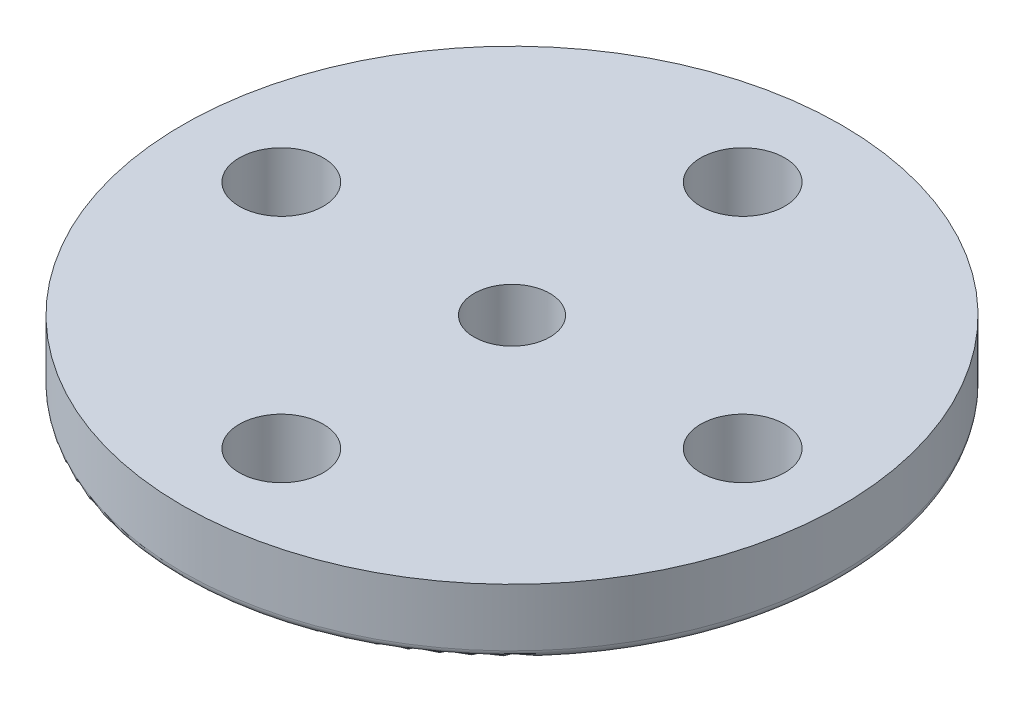
SolidWorks part; units mm, degrees
material "ABS"
ref_plane "Front Plane" through (0, 0, 0) normal (0, 0, 1) x (1, 0, 0)
ref_plane "Top Plane" through (0, 0, 0) normal (0, 1, 0) x (1, 0, 0)
ref_plane "Right Plane" through (0, 0, 0) normal (1, 0, 0) x (0, 0, -1)
sketch "Sketch1" plane through (0, 0, 0) normal (0, 1, 0) x (1, 0, 0)
  circle A0 centre (0, 0) radius 10
  dimension "D1" = 20
extrude "Boss-Extrude1" add sketch "Sketch1" along normal blind 2
sketch "Sketch2" plane through (0, 0, 0) normal (0, 1, 0) x (1, 0, 0)
  circle A0 centre (0, 0) radius 4.5
  dimension "D1" = 9
extrude "Boss-Extrude2" add sketch "Sketch2" against normal blind 3.5
sketch "Sketch3" plane through (0, 0, 0) normal (0, 1, 0) x (1, 0, 0)
  line L0 (0, 16.6668) -> (0, -17.2828) construction
  line L1 (-21.9372, 0) -> (30.2192, 0) construction
  line L2 (-7, 16.6668) -> (-7, -16.6668) construction
  line L3 (-15.9139, 7) -> (17.4197, 7) construction
  circle A0 centre (0, 7) radius 1.275
  circle A1 centre (-7, 0) radius 1.275
  circle A2 centre (0, -7) radius 1.275
  circle A3 centre (7, 0) radius 1.275
  dimension "D3" = 2.55
  dimension "D4" = 2.55
  dimension "D1" = 7
  dimension "D2" = 7
extrude "Cut-Extrude1" cut sketch "Sketch3" along normal through all
cosmetic thread "Cosmetic Thread1" parameters "D2"=2.87
cosmetic thread "Cosmetic Thread2" parameters "D2"=2.87
cosmetic thread "Cosmetic Thread3" parameters "D2"=2.87
cosmetic thread "Cosmetic Thread4" parameters "D2"=2.87
fillet "Fillet1" radius 0.25 1 edges at (0, 0, 10)
sketch "Sketch6" plane through (0, 2, 0) normal (0, 1, 0) x (1, 0, 0)
  circle A0 centre (0, 0) radius 1.15
  dimension "D1" = 2.3
extrude "Cut-Extrude2" cut sketch "Sketch6" against normal through all
sketch "Sketch7" plane through (0, -3.5, 0) normal (0, -1, 0) x (1, 0, 0)
  circle A0 centre (0, 0) radius 3.05
  dimension "D1" = 6.1
extrude "Cut-Extrude3" cut sketch "Sketch7" against normal blind 2.5
sketch3d "3DSketch1"
  line L0 (0, 0, 0) -> (0, -47.4119, 0) construction
sketch "Sketch8" plane through (0, -3.5, 0) normal (0, -1, 0) x (1, 0, 0)
  line L1 (-2.4783, -1.1025) -> (-2.8739, -0.9985)
  line L2 (-2.4783, -1.1025) -> (-2.6494, -1.474)
  arc A1 (-2.8739, -0.9985) -> (-2.6494, -1.474) centre (-0.15, -0.0034) ccw
  circle A4 centre (0, 0) radius 3.05 construction
  dimension "D4" = 0.409
  dimension "D3" = 5.8
  dimension "D1" = 80
  dimension "D2" = 0.5258
extrude "Boss-Extrude4" add sketch "Sketch8" against normal blind 2.5
pattern_circular "CirPattern1" count 26 over 360 about axis through (0, 0, 0) along (0, -1, 0) of "Boss-Extrude4"
